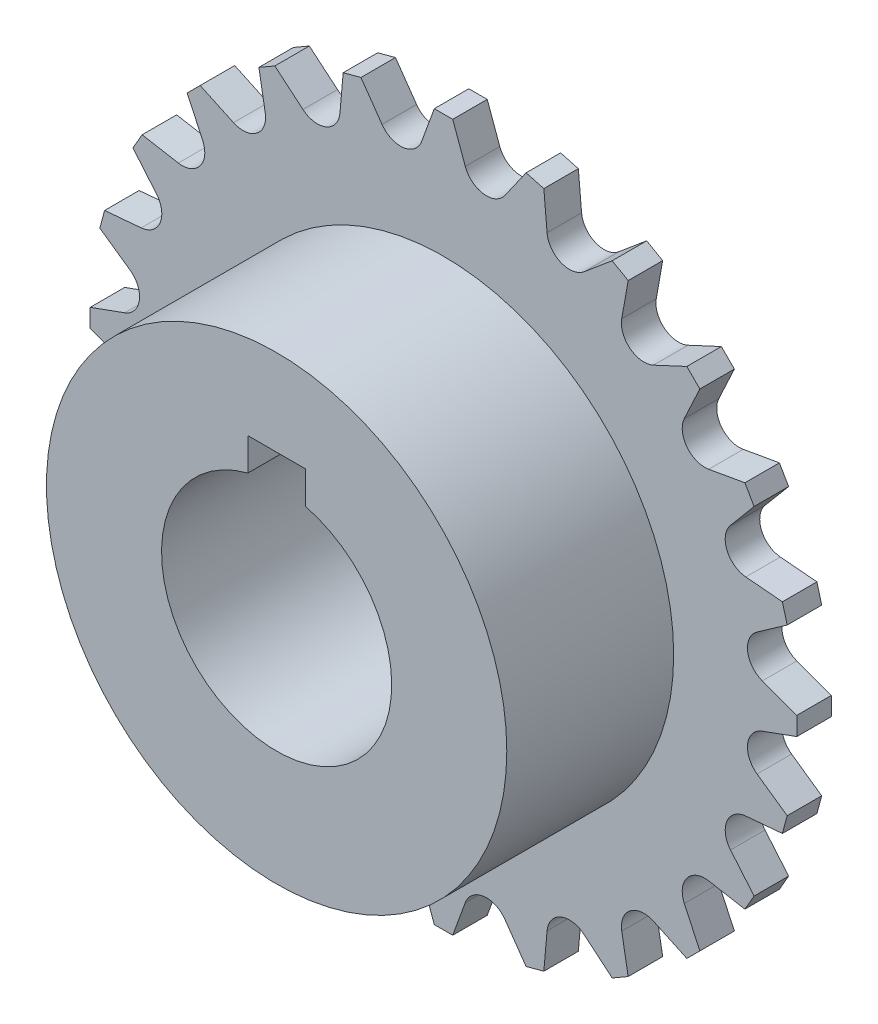
SolidWorks part; units mm, degrees
ref_plane "Front Plane" through (0, 0, 0) normal (0, 0, 1) x (1, 0, 0)
ref_plane "Top Plane" through (0, 0, 0) normal (0, 1, 0) x (1, 0, 0)
ref_plane "Right Plane" through (0, 0, 0) normal (1, 0, 0) x (0, 0, -1)
sketch "Sketch1" plane through (0, 0, 0) normal (0, 0, 1) x (1, 0, 0)
  line L0 (0, 15.875) -> (0, 12.7) construction
  line L2 (-3.175, 12.2967) -> (-3.175, 15.875)
  line L3 (-3.175, 15.875) -> (3.175, 15.875)
  line L4 (3.175, 12.2967) -> (3.175, 15.875)
  line L5 (-1.016, 38.989) -> (1.016, 38.989)
  line L10 (1.016, 38.989) -> (2.4027, 35.179)
  line L11 (0, 38.989) -> (0, 0) construction
  line L12 (-1.016, 38.989) -> (-2.4027, 35.179)
  line L13 (-2.4027, 35.179) -> (0, 0) construction
  line L14 (0, 0) -> (6.7841, 34.6022) construction
  line L84 (11.0725, 37.3975) -> (11.4259, 33.3584)
  line L85 (9.1097, 37.9234) -> (11.0725, 37.3975)
  line L86 (9.1097, 37.9234) -> (6.7841, 34.6022)
  line L87 (20.3744, 33.2575) -> (19.6703, 29.2645)
  line L88 (18.6146, 34.2735) -> (20.3744, 33.2575)
  line L89 (18.6146, 34.2735) -> (15.5087, 31.6673)
  line L90 (28.2878, 26.851) -> (26.5743, 23.1763)
  line L91 (26.851, 28.2878) -> (28.2878, 26.851)
  line L92 (26.851, 28.2878) -> (23.1763, 26.5743)
  line L93 (34.2735, 18.6146) -> (31.6673, 15.5087)
  line L94 (33.2575, 20.3744) -> (34.2735, 18.6146)
  line L95 (33.2575, 20.3744) -> (29.2645, 19.6703)
  line L96 (37.9234, 9.1097) -> (34.6022, 6.7841)
  line L97 (37.3975, 11.0725) -> (37.9234, 9.1097)
  line L98 (37.3975, 11.0725) -> (33.3584, 11.4259)
  line L99 (38.989, -1.016) -> (35.179, -2.4027)
  line L100 (38.989, 1.016) -> (38.989, -1.016)
  line L101 (38.989, 1.016) -> (35.179, 2.4027)
  line L102 (37.3975, -11.0725) -> (33.3584, -11.4259)
  line L103 (37.9234, -9.1097) -> (37.3975, -11.0725)
  line L104 (37.9234, -9.1097) -> (34.6022, -6.7841)
  line L105 (33.2575, -20.3744) -> (29.2645, -19.6703)
  line L106 (34.2735, -18.6146) -> (33.2575, -20.3744)
  line L107 (34.2735, -18.6146) -> (31.6673, -15.5087)
  line L108 (26.851, -28.2878) -> (23.1763, -26.5743)
  line L109 (28.2878, -26.851) -> (26.851, -28.2878)
  line L110 (28.2878, -26.851) -> (26.5743, -23.1763)
  line L111 (18.6146, -34.2735) -> (15.5087, -31.6673)
  line L112 (20.3744, -33.2575) -> (18.6146, -34.2735)
  line L113 (20.3744, -33.2575) -> (19.6703, -29.2645)
  line L114 (9.1097, -37.9234) -> (6.7841, -34.6022)
  line L115 (11.0725, -37.3975) -> (9.1097, -37.9234)
  line L116 (11.0725, -37.3975) -> (11.4259, -33.3584)
  line L117 (-1.016, -38.989) -> (-2.4027, -35.179)
  line L118 (1.016, -38.989) -> (-1.016, -38.989)
  line L119 (1.016, -38.989) -> (2.4027, -35.179)
  line L120 (-11.0725, -37.3975) -> (-11.4259, -33.3584)
  line L121 (-9.1097, -37.9234) -> (-11.0725, -37.3975)
  line L122 (-9.1097, -37.9234) -> (-6.7841, -34.6022)
  line L123 (-20.3744, -33.2575) -> (-19.6703, -29.2645)
  line L124 (-18.6146, -34.2735) -> (-20.3744, -33.2575)
  line L125 (-18.6146, -34.2735) -> (-15.5087, -31.6673)
  line L126 (-28.2878, -26.851) -> (-26.5743, -23.1763)
  line L127 (-26.851, -28.2878) -> (-28.2878, -26.851)
  line L128 (-26.851, -28.2878) -> (-23.1763, -26.5743)
  line L129 (-34.2735, -18.6146) -> (-31.6673, -15.5087)
  line L130 (-33.2575, -20.3744) -> (-34.2735, -18.6146)
  line L131 (-33.2575, -20.3744) -> (-29.2645, -19.6703)
  line L132 (-37.9234, -9.1097) -> (-34.6022, -6.7841)
  line L133 (-37.3975, -11.0725) -> (-37.9234, -9.1097)
  line L134 (-37.3975, -11.0725) -> (-33.3584, -11.4259)
  line L135 (-38.989, 1.016) -> (-35.179, 2.4027)
  line L136 (-38.989, -1.016) -> (-38.989, 1.016)
  line L137 (-38.989, -1.016) -> (-35.179, -2.4027)
  line L138 (-37.3975, 11.0725) -> (-33.3584, 11.4259)
  line L139 (-37.9234, 9.1097) -> (-37.3975, 11.0725)
  line L140 (-37.9234, 9.1097) -> (-34.6022, 6.7841)
  line L141 (-33.2575, 20.3744) -> (-29.2645, 19.6703)
  line L142 (-34.2735, 18.6146) -> (-33.2575, 20.3744)
  line L143 (-34.2735, 18.6146) -> (-31.6673, 15.5087)
  line L144 (-26.851, 28.2878) -> (-23.1763, 26.5743)
  line L145 (-28.2878, 26.851) -> (-26.851, 28.2878)
  line L146 (-28.2878, 26.851) -> (-26.5743, 23.1763)
  line L147 (-18.6146, 34.2735) -> (-15.5087, 31.6673)
  line L148 (-20.3744, 33.2575) -> (-18.6146, 34.2735)
  line L149 (-20.3744, 33.2575) -> (-19.6703, 29.2645)
  line L150 (-9.1097, 37.9234) -> (-6.7841, 34.6022)
  line L151 (-11.0725, 37.3975) -> (-9.1097, 37.9234)
  line L152 (-11.0725, 37.3975) -> (-11.4259, 33.3584)
  arc A0 (-3.175, 12.2967) -> (3.175, 12.2967) centre (0, 0) ccw
  circle A1 centre (0, 0) radius 25.4
  arc A2 (2.4027, 35.179) -> (6.7841, 34.6022) centre (4.7436, 36.031) ccw
  arc A3 (11.4259, 33.3584) -> (15.5087, 31.6673) centre (13.9074, 33.5755) ccw
  arc A4 (19.6703, 29.2645) -> (23.1763, 26.5743) centre (22.1236, 28.832) ccw
  arc A5 (26.5743, 23.1763) -> (29.2645, 19.6703) centre (28.832, 22.1236) ccw
  arc A6 (31.6673, 15.5087) -> (33.3584, 11.4259) centre (33.5755, 13.9074) ccw
  arc A7 (34.6022, 6.7841) -> (35.179, 2.4027) centre (36.031, 4.7436) ccw
  arc A8 (35.179, -2.4027) -> (34.6022, -6.7841) centre (36.031, -4.7436) ccw
  arc A9 (33.3584, -11.4259) -> (31.6673, -15.5087) centre (33.5755, -13.9074) ccw
  arc A10 (29.2645, -19.6703) -> (26.5743, -23.1763) centre (28.832, -22.1236) ccw
  arc A11 (23.1763, -26.5743) -> (19.6703, -29.2645) centre (22.1236, -28.832) ccw
  arc A12 (15.5087, -31.6673) -> (11.4259, -33.3584) centre (13.9074, -33.5755) ccw
  arc A13 (6.7841, -34.6022) -> (2.4027, -35.179) centre (4.7436, -36.031) ccw
  arc A14 (-2.4027, -35.179) -> (-6.7841, -34.6022) centre (-4.7436, -36.031) ccw
  arc A15 (-11.4259, -33.3584) -> (-15.5087, -31.6673) centre (-13.9074, -33.5755) ccw
  arc A16 (-19.6703, -29.2645) -> (-23.1763, -26.5743) centre (-22.1236, -28.832) ccw
  arc A17 (-26.5743, -23.1763) -> (-29.2645, -19.6703) centre (-28.832, -22.1236) ccw
  arc A18 (-31.6673, -15.5087) -> (-33.3584, -11.4259) centre (-33.5755, -13.9074) ccw
  arc A19 (-34.6022, -6.7841) -> (-35.179, -2.4027) centre (-36.031, -4.7436) ccw
  arc A20 (-35.179, 2.4027) -> (-34.6022, 6.7841) centre (-36.031, 4.7436) ccw
  arc A21 (-33.3584, 11.4259) -> (-31.6673, 15.5087) centre (-33.5755, 13.9074) ccw
  arc A22 (-29.2645, 19.6703) -> (-26.5743, 23.1763) centre (-28.832, 22.1236) ccw
  arc A23 (-23.1763, 26.5743) -> (-19.6703, 29.2645) centre (-22.1236, 28.832) ccw
  arc A24 (-15.5087, 31.6673) -> (-11.4259, 33.3584) centre (-13.9074, 33.5755) ccw
  arc A25 (-6.7841, 34.6022) -> (-2.4027, 35.179) centre (-4.7436, 36.031) ccw
  point P4 (0, 12.7)
  dimension "D2" = 25.4
  dimension "D1" = 50.8
  dimension "D3" = 6.35
  dimension "D4" = 3.175
  dimension "D5" = 2.032
  dimension "D6" = 110
  dimension "D7" = 3.81
  dimension "D9" = 15
  dimension "D8" = 38.989
  dimension "D10" = 24
extrude "Boss-Extrude1" add sketch "Sketch1" along normal blind 3.81 contours A25 L150 L151 L152 A24 L147 L148 L149 A23 L144 L145 L146 A22 L141 L142 L143 A21 L138 L139 L140 A20 L135 L136 L137 A19 L132 L133 L134 A18 L129 L130 L131 A17 L126 L127 L128 A16 L123 L124 L125 A15 L120 L121 L122 A14 L117 L118 L119 A13 L114 L115 region at (0, 37.8862, 0)
extrude "Boss-Extrude2" add sketch "Sketch1<3>" along normal blind 22.225 contours A1 A0 L2 L3 L4 region at (-24.6816, 0, 0)
sketch "Sketch1<3>" plane through (0, 0, 0) normal (0, 0, 1) x (1, 0, 0) same geometry as "Sketch1"
equation "\"Radius\"= 1.535"
equation "\"D8@Sketch1\" = \"Radius\""
